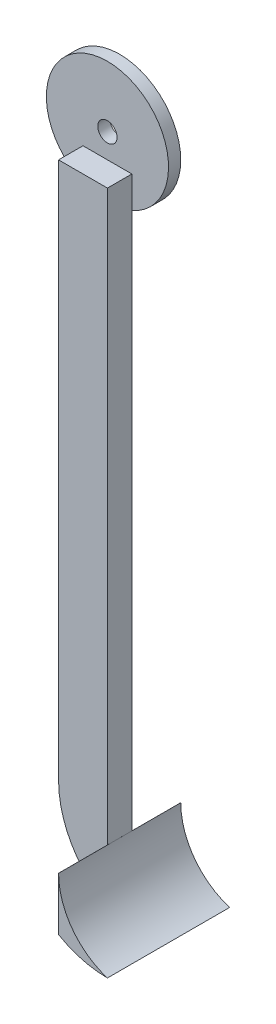
SolidWorks part; units mm, degrees
ref_plane "Front Plane" through (0, 0, 0) normal (0, 0, 1) x (1, 0, 0)
ref_plane "Top Plane" through (0, 0, 0) normal (0, 1, 0) x (1, 0, 0)
ref_plane "Right Plane" through (0, 0, 0) normal (1, 0, 0) x (0, 0, -1)
sketch "Sketch3" plane through (0, 0, 0) normal (0, 0, 1) x (1, 0, 0)
  line L0 (0, 0) -> (88.5471, 0)
  line L1 (0.275, 0) -> (-0.275, 0) construction
  line L2 (88.5471, 0) -> (-88.9153, 0)
  line L3 (0, 0) -> (0, 55.5951)
  line L4 (0, -0.275) -> (0, 0.275) construction
  line L5 (0, 55.5951) -> (0, -54.6746)
  circle A4 centre (0, 0) radius 1.975
  circle A5 centre (0, 0) radius 12.5
extrude "Boss-Extrude5" add sketch "Sketch3" along normal blind 2.5 contours L5 A5 L2 A4 | L2 A5 L5 A4 | L5 A5 L2 A4 | L2 A5 L5 A4 region at (5.4195, 5.4195, 0) region at (5.4195, -5.4195, 0) region at (-5.4195, -5.4195, 0) region at (-5.4195, 5.4195, 0)
ref_plane "Plane7" through (0, 0, 2.5) normal (0, 0, 1) x (1, 0, 0)
sketch "Sketch5" plane through (0, 0, 2.5) normal (0, 0, 1) x (1, 0, 0)
  line L0 (0, -1.975) -> (0, -4.975)
  line L1 (0, -4.975) -> (5, -4.975)
  line L2 (0, -4.975) -> (-5, -4.975)
  line L3 (5, -4.975) -> (5, -134.975)
  line L4 (5, -134.975) -> (-5, -134.975)
  line L5 (-5, -134.975) -> (-5, -4.975)
  circle A0 centre (0, 0) radius 1.975 construction
extrude "Boss-Extrude6" add sketch "Sketch5" along normal blind 5 contours L5 L4 L3 L1 L2 region at (0, -69.975, 2.5)
ref_plane "Plane8" through (5, 0, 0) normal (1, 0, 0) x (0, 0, -1)
sketch "Sketch6" plane through (5, 0, 0) normal (1, 0, 0) x (0, 0, -1)
  line L0 (-7.5, -134.975) -> (-2.5, -134.975)
  line L12 (-30, -136.4037) -> (-30, -121.4037)
  line L13 (-30, -121.4037) -> (20, -121.4037)
  line L14 (20, -121.4037) -> (20, -134.975)
  line L15 (-30, -136.4037) -> (-30, -161.4037)
  line L16 (-30, -161.4037) -> (20, -161.4037)
  line L17 (20, -161.4037) -> (20, -134.975)
  dimension "D1" = 40
ref_plane "Plane9" through (0, 0, 2.5) normal (0, 0, -1) x (-1, 0, 0)
sketch "Sketch11" plane through (0, 0, 2.5) normal (0, 0, -1) x (-1, 0, 0)
  line L1 (-5, -134.975) -> (-5.0036, -121.4037)
sketch "Sketch13" plane through (5, 0, 0) normal (1, 0, 0) x (0, 0, -1)
  line L0 (-7.5, -134.975) -> (-17.5, -134.975)
  line L1 (-17.5, -134.975) -> (-17.5, -121.4037)
  line L2 (-30, -121.4037) -> (20, -121.4037) construction
  line L3 (-17.5, -121.4037) -> (-7.5, -121.4037)
  line L4 (-7.5, -4.975) -> (-7.5, -134.975) construction
  line L5 (-7.5, -121.4037) -> (-2.5, -121.4037)
  line L6 (-2.5, -5.5) -> (-2.5, 5.5) construction
  line L7 (-2.5, -121.4037) -> (7.5, -121.4037)
  line L8 (7.5, -121.4037) -> (7.5, -134.975)
  line L9 (7.5, -134.975) -> (-2.5, -134.975)
  line L10 (-2.5, -134.975) -> (-7.5, -134.975)
  dimension "D1" = 10
  dimension "D2" = 10
extrude "Boss-Extrude10" add sketch "Sketch13" along normal blind 10
sketch "Sketch14" plane through (0, 0, -7.5) normal (0, 0, -1) x (-1, 0, 0)
  line L0 (-15, -134.975) -> (-15, -121.4037)
  line L1 (-15, -121.4037) -> (-5.0036, -121.4037)
  arc A1 (-5.0036, -121.4037) -> (-15, -134.975) centre (-19.2142, -121.4037) cw
extrude "Cut-Extrude2" cut sketch "Sketch14" against normal through all
fillet "Fillet2" radius 20 1 edges at (-5, -134.975, 5)
